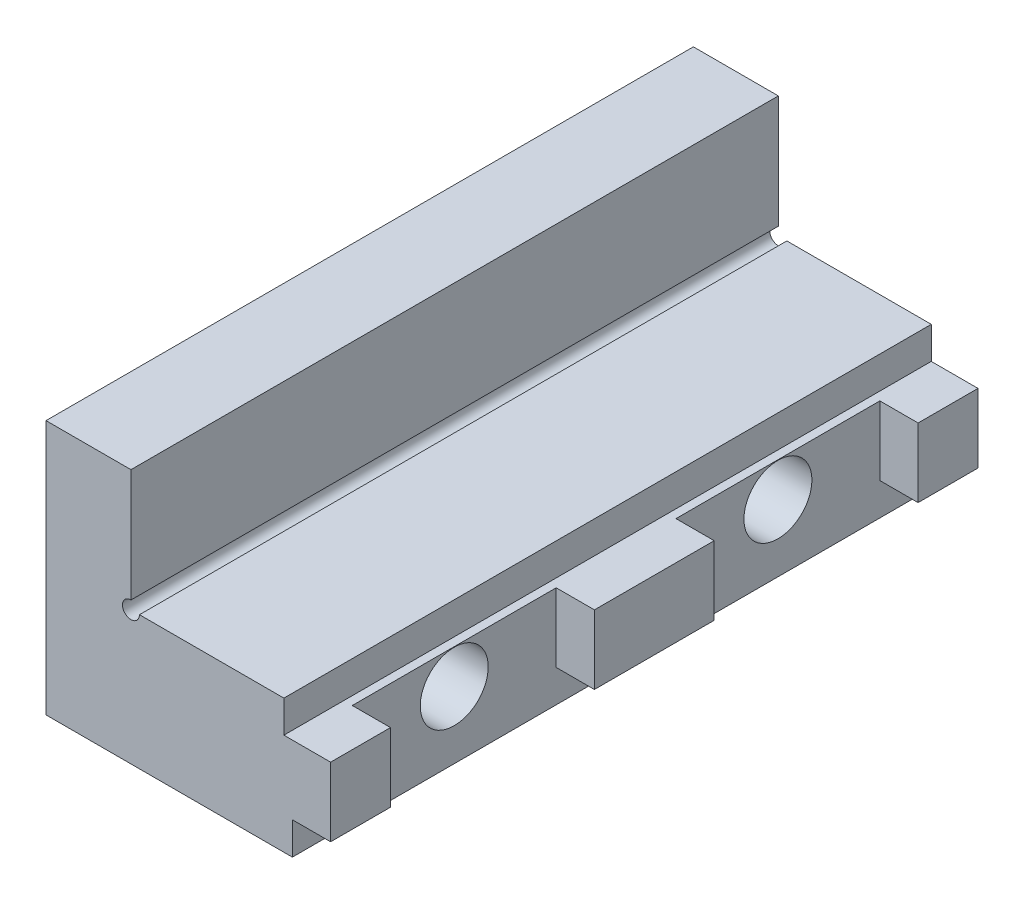
SolidWorks part; units mm, degrees
ref_plane "Front Plane" through (0, 0, 0) normal (0, 0, 1) x (1, 0, 0)
ref_plane "Top Plane" through (0, 0, 0) normal (0, 1, 0) x (1, 0, 0)
ref_plane "Right Plane" through (0, 0, 0) normal (1, 0, 0) x (0, 0, -1)
sketch "Sketch1" plane through (0, 0, 0) normal (0, 0, 1) x (1, 0, 0)
  line L0 (-10, -15.715) -> (-10, 14.285)
  line L1 (-10, 14.285) -> (0, 14.285)
  line L2 (0, 14.285) -> (0, 1)
  line L3 (1, 0) -> (18, 0)
  line L4 (18, 0) -> (18, -3.78)
  line L5 (19, -15.715) -> (-10, -15.715)
  line L6 (0, 1) -> (0, 0) construction
  line L7 (0, 0) -> (1, 0) construction
  line L8 (18, -3.78) -> (23.5, -3.78)
  line L9 (23.5, -3.78) -> (23.5, -11.9)
  line L10 (23.5, -11.9) -> (19, -11.9)
  line L11 (21.2322, -7.84) -> (23.5, -7.84) construction
  line L12 (19, -11.9) -> (19, -15.715)
  arc A0 (0, 1) -> (1, 0) centre (0, 0) ccw
  point P15 (0, 0)
  point P16 (0, 0)
  point P17 (-2.2322, -1.3618)
  dimension "D4" = 2
  dimension "D1" = 18
  dimension "D2" = 10
  dimension "D3" = 30
  dimension "D5" = 15.715
  dimension "D6" = 8.12
  dimension "D7" = 4.5
  dimension "D8" = 3.815
  dimension "D9" = 19
extrude "Boss-Extrude1" add sketch "Sketch1" against normal blind 38.1 and the other way blind 38.1 contours A0 L2 L1 L0 L5 L4 L3 | L10 L9 L8 L4 region at (3.2488, -4.5146, 0)
sketch "Sketch2" plane through (0, 0, 0) normal (1, 0, 0) x (0, 0, -1)
  line L0 (-19.05, -7.84) -> (19.05, -7.84) construction
  line L1 (-38.1, -7.84) -> (-19.05, -7.84) construction
  line L2 (-38.1, -3.78) -> (-38.1, -11.9) construction
  line L3 (0, 0) -> (0, -7.84) construction
  circle A0 centre (-19.05, -7.84) radius 4
  circle A1 centre (19.05, -7.84) radius 4
  dimension "D4" = 8
  dimension "D3" = 38.1
extrude "Cut-Extrude1" cut sketch "Sketch2" along normal blind 55.4 and the other way blind 30
sketch "Sketch3" plane through (0, 0, 0) normal (1, 0, 0) x (0, 0, -1)
  circle A0 centre (-19.05, -7.84) radius 6.5
  circle A1 centre (19.05, -7.84) radius 6.5
  dimension "D1" = 13
extrude "Cut-Extrude2" cut sketch "Sketch3" against normal blind 18.2
sketch "Sketch4" plane through (0, 0, 0) normal (1, 0, 0) x (0, 0, -1)
  line L0 (-19.05, -7.84) -> (19.05, -7.84) construction
  line L1 (0, 0) -> (0, -7.84) construction
  line L3 (-31.05, -17.84) -> (-7.05, -17.84)
  line L4 (-31.05, -17.84) -> (-31.05, 2.16)
  line L5 (-31.05, 2.16) -> (-7.05, 2.16)
  line L6 (-7.05, -17.84) -> (-7.05, 2.16)
  line L7 (-31.05, -17.84) -> (-7.05, 2.16) construction
  line L8 (-31.05, 2.16) -> (-7.05, -17.84) construction
  line L9 (7.05, 2.16) -> (31.05, 2.16)
  line L10 (7.05, 2.16) -> (7.05, -17.84)
  line L11 (7.05, -17.84) -> (31.05, -17.84)
  line L12 (31.05, 2.16) -> (31.05, -17.84)
  line L13 (7.05, 2.16) -> (31.05, -17.84) construction
  line L14 (7.05, -17.84) -> (31.05, 2.16) construction
  dimension "D1" = 24
  dimension "D2" = 24
  dimension "D3" = 20
  dimension "D4" = 20
extrude "Cut-Extrude3" cut sketch "Sketch4" along normal blind 10 from surface starting at face at (19, -13.8075, 0)
